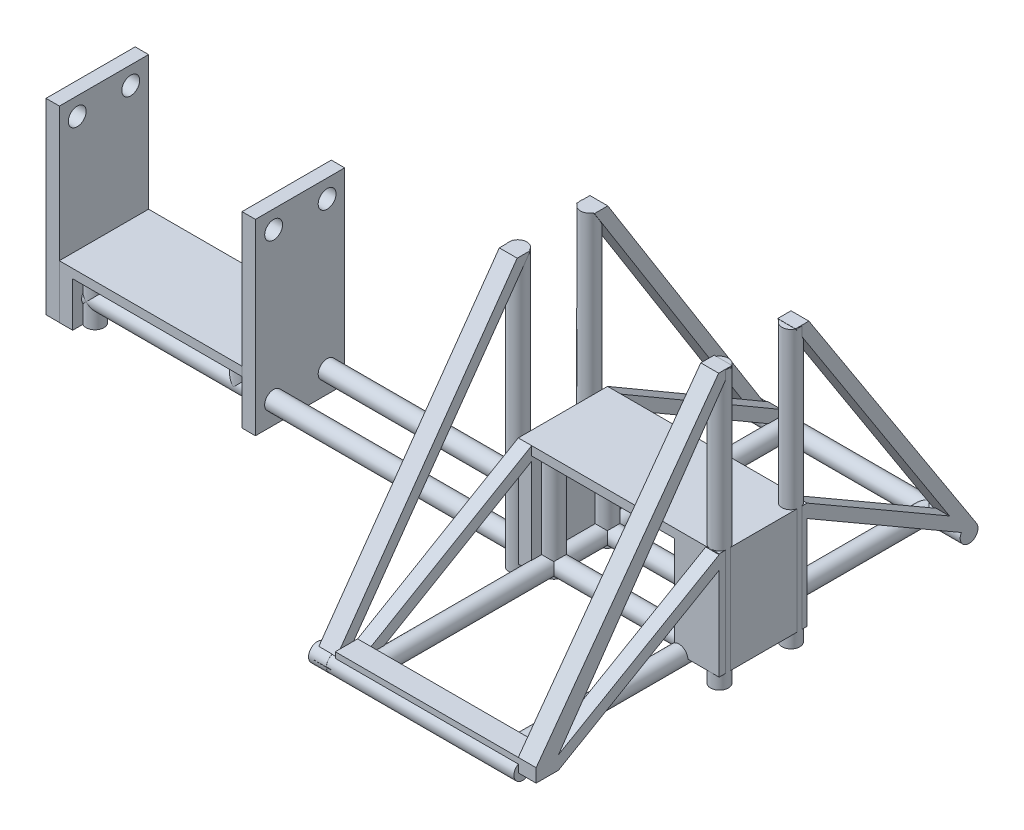
SolidWorks part; units mm, degrees
ref_plane "Front Plane" through (0, 0, 0) normal (0, 0, 1) x (1, 0, 0)
ref_plane "Top Plane" through (0, 0, 0) normal (0, 1, 0) x (1, 0, 0)
ref_plane "Right Plane" through (0, 0, 0) normal (1, 0, 0) x (0, 0, -1)
sketch "Sketch1" plane through (0, 0, 0) normal (0, 1, 0) x (1, 0, 0)
  line L0 (-25.6839, 52.3309) -> (15.3161, 52.3309)
  line L1 (-25.6839, 52.3309) -> (-25.6839, 72.3309)
  line L2 (-25.6839, 72.3309) -> (15.3161, 72.3309)
  line L3 (15.3161, 72.3309) -> (15.3161, 52.3309)
extrude "Boss-Extrude2" add sketch "Sketch1" along normal blind 2
sketch "Sketch2" plane through (0, 0, 0) normal (0, -1, 0) x (-1, 0, 0)
  circle A1 centre (21.6839, 56.3309) radius 2
  circle A4 centre (21.6839, 68.3309) radius 2
  point P2 (21.6839, 56.3309)
  point P3 (0, 0)
  point P14 (0, 0)
extrude "Boss-Extrude5" add sketch "Sketch2" along normal blind 10
sketch "Sketch4" plane through (0, 0, 0) normal (0, -1, 0) x (-1, 0, 0)
  circle A1 centre (-11.3161, 56.3309) radius 2
  circle A2 centre (-11.3161, 68.3309) radius 2
extrude "Boss-Extrude6" add sketch "Sketch4" along normal blind 5
sketch "Sketch5" plane through (15.3161, 0, 0) normal (1, 0, 0) x (0, 0, -1)
  circle A3 centre (56.3309, -4.9901) radius 2
  circle A4 centre (68.3309, -4.9901) radius 2
extrude "Boss-Extrude7" add sketch "Sketch5" against normal blind 38 and the other way blind 100
sketch "Sketch6" plane through (0, 2, 0) normal (0, 1, 0) x (1, 0, 0)
  circle A1 centre (113.1107, 56.3309) radius 2
  circle A2 centre (113.1107, 68.3309) radius 2
  circle A3 centre (81.1107, 68.3309) radius 2
  circle A4 centre (81.1107, 56.3309) radius 2
extrude "Boss-Extrude8" add sketch "Sketch6" along normal blind 15 and the other way blind 9
sketch "Sketch7" plane through (0, 17, 0) normal (0, 1, 0) x (1, 0, 0)
  line L2 (77.1107, 56.3309) -> (77.1107, 52.3666)
  line L4 (77.1107, 52.3666) -> (118.1107, 52.3666)
  line L5 (77.1107, 52.3666) -> (77.1107, 72.3666)
  line L6 (77.1107, 72.3666) -> (118.1107, 72.3666)
  line L7 (118.1107, 52.3666) -> (118.1107, 72.3666)
extrude "Boss-Extrude9" add sketch "Sketch7" along normal blind 2 contours L5 L4 L7 L6
sketch "Sketch8" plane through (0, 0, -52.3666) normal (0, 0, 1) x (1, 0, 0)
  circle A1 centre (81.1107, -4.9901) radius 2
  circle A2 centre (113.1107, -4.9901) radius 2
extrude "Boss-Extrude10" add sketch "Sketch8" along normal blind 40 and the other way blind 56
sketch "Sketch9" plane through (118.1107, 0, 0) normal (1, 0, 0) x (0, 0, -1)
  line L1 (12.3666, -2.9901) -> (12.3666, -6.9901) construction
  line L2 (108.3666, -6.9901) -> (108.3666, -2.9901) construction
  circle A1 centre (12.3666, -4.9901) radius 1.9797
  circle A2 centre (108.3666, -4.9901) radius 2
extrude "Boss-Extrude11" add sketch "Sketch9" against normal blind 42
sketch "Sketch12" plane through (77.1107, 0, 0) normal (-1, 0, 0) x (0, 0, 1)
  line L0 (-52.3666, 19) -> (-52.3666, 17) construction
  line L1 (-52.3666, 19) -> (-72.3666, 19)
  line L2 (-52.3666, 19) -> (-52.3666, -5.472)
  line L3 (-52.3666, -5.472) -> (-72.3666, -5.472)
  line L4 (-72.3666, 19) -> (-72.3666, -5.472)
  point P4 (-72.3666, 19)
  point P6 (-52.3666, 19)
  point P9 (0, 0)
  point P10 (-72.3666, -5.472)
extrude "Boss-Extrude15" add sketch "Sketch12" against normal blind 3
sketch "Sketch14" plane through (0, 19, 0) normal (0, 1, 0) x (1, 0, 0)
  circle A2 centre (75.0364, 70.3666) radius 2
  circle A3 centre (75.0364, 54.3666) radius 2
  circle A4 centre (120.1851, 70.3666) radius 2
  circle A5 centre (120.1851, 54.3666) radius 2
extrude "Boss-Extrude17" add sketch "Sketch14" against normal blind 27 and the other way blind 35
sketch "Sketch15" plane through (118.1107, 0, 0) normal (1, 0, 0) x (0, 0, -1)
  line L1 (52.3666, 19) -> (72.0796, 19)
  line L2 (52.3666, 19) -> (52.3666, -4.9227)
  line L3 (52.3666, -4.9227) -> (72.0796, -4.9227)
  line L4 (72.0796, 19) -> (72.0796, -4.9227)
  point P5 (72.0796, -4.9227)
extrude "Boss-Extrude18" add sketch "Sketch15" along normal blind 4 and the other way blind 6
sketch "Sketch17" plane through (-25.6839, 0, 0) normal (-1, 0, 0) x (0, 0, 1)
  line L1 (-72.3309, 2) -> (-52.3309, 2)
  line L2 (-72.3309, 2) -> (-72.3309, -10)
  line L3 (-72.3309, -10) -> (-52.3309, -10)
  line L4 (-52.3309, 2) -> (-52.3309, -10)
extrude "Boss-Extrude20" add sketch "Sketch17" against normal blind 3
sketch "Sketch19" plane through (15.3161, 0, 0) normal (1, 0, 0) x (0, 0, -1)
  line L7 (52.2692, -9.9436) -> (72.2692, -9.9436)
  line L8 (52.2692, -9.9436) -> (52.2692, 32.0564)
  line L9 (52.2692, 32.0564) -> (72.2692, 32.0564)
  line L10 (72.2692, -9.9436) -> (72.2692, 32.0564)
extrude "Boss-Extrude23" add sketch "Sketch19" along normal blind 3
sketch "Sketch21" plane through (-25.6839, 0, 0) normal (-1, 0, 0) x (0, 0, 1)
  line L1 (-72.3309, -10) -> (-52.349, -10)
  line L2 (-72.3309, -10) -> (-72.3309, 32)
  line L3 (-72.3309, 32) -> (-52.349, 32)
  line L4 (-52.349, -10) -> (-52.349, 32)
extrude "Boss-Extrude24" add sketch "Sketch21" along normal blind 3
sketch "Sketch22" plane through (-28.6839, 0, 0) normal (-1, 0, 0) x (0, 0, 1)
  circle A1 centre (-68.3309, 28) radius 2
  circle A2 centre (-56.349, 28) radius 2
extrude "Cut-Extrude1" cut sketch "Sketch22" against normal blind 52
sketch "Sketch23" plane through (77.1107, 0, 0) normal (-1, 0, 0) x (0, 0, 1)
  line L0 (-72.3666, 19) -> (-72.3666, 16)
  line L2 (-72.3666, 19) -> (-108.3666, -1.9901)
  line L3 (-72.3666, 16) -> (-108.3666, -4.9901)
  line L4 (-108.3666, -1.9901) -> (-108.3666, -4.9901)
  line L5 (-72.3666, 19) -> (-72.3666, -5.472) construction
  line L6 (-62.3666, 19) -> (-62.3666, 7.5165)
  line L7 (-52.3666, 19) -> (-72.3666, 19) construction
  line L8 (-52.3666, 16) -> (-16.3666, -4.9901)
  line L9 (-16.3666, -1.9901) -> (-16.3666, -4.9901)
  line L10 (-52.3666, 19) -> (-16.3666, -1.9901)
  line L11 (-52.3666, 19) -> (-52.3666, 16)
  point P17 (-16.3666, -4.9901)
  point P18 (-16.3666, -4.9901)
  point P19 (0, 0)
  line M10 (-72.3666, 19) -> (-72.3666, -5.472)
  line M16 (-52.3666, -5.472) -> (-52.3666, 19)
extrude "Boss-Extrude25" add sketch "Sketch23" against normal blind 3 contours L2 L4 L3 M10 | L10 L8 L9 M16 region at (77.1107, 7.005, -90.3666) region at (77.1107, 7.005, -34.3666)
sketch "Sketch24" plane through (122.1107, 0, 0) normal (1, 0, 0) x (0, 0, -1)
  line L0 (72.0796, 19) -> (72.0796, 16)
  line L1 (72.0796, 19) -> (108.3666, -1.9901)
  line L2 (72.0796, 16) -> (108.3666, -4.9901)
  line L3 (108.3666, -1.9901) -> (108.3666, -4.9901)
  line L4 (72.0796, -4.9227) -> (72.0796, 19) construction
  line L5 (62.3666, 19) -> (62.3666, 13.064)
  line L6 (69.8263, 19) -> (54.9069, 19) construction
  line L7 (52.6536, 16) -> (16.3666, -4.9901)
  line L8 (16.3666, -1.9901) -> (16.3666, -4.9901)
  line L9 (52.6536, 19) -> (16.3666, -1.9901)
  line L10 (52.6536, 19) -> (52.6536, 16)
extrude "Boss-Extrude26" add sketch "Sketch24" against normal blind 3 contours L10 L9 L8 L7 | L2 L3 L1 L0 region at (122.1107, 7.005, -34.5101)
sketch "Sketch25" plane through (118.1107, 0, 0) normal (1, 0, 0) x (0, 0, -1)
  circle A1 centre (108.3666, -4.9901) radius 2
extrude "Boss-Extrude27" add sketch "Sketch25" along normal blind 4
sketch "Sketch26" plane through (0, 0, -16.3666) normal (0, 0, 1) x (1, 0, 0)
  line L1 (77.1107, -4.9901) -> (122.1107, -4.9901)
  line L2 (77.1107, -4.9901) -> (77.1107, -1.9901)
  line L3 (77.1107, -1.9901) -> (122.1107, -1.9901)
  line L4 (122.1107, -4.9901) -> (122.1107, -1.9901)
  point P4 (0, 0)
  point P5 (76.2247, -2.6666)
  point P6 (77.1107, -1.9901)
  point P8 (77.1107, -4.9901)
  point P10 (104.7634, -1.9901)
  point P11 (122.1107, -1.9901)
extrude "Boss-Extrude28" add sketch "Sketch26" along normal blind 5
sketch "Sketch28" plane through (122.1107, 0, 0) normal (1, 0, 0) x (0, 0, -1)
  line L0 (72.0796, 16) -> (106.6353, -3.9886) construction
  line L1 (11.3666, -1.9901) -> (16.3666, -1.9901)
  line L2 (11.3666, -1.9901) -> (52.2585, 54.1126)
  line L3 (16.3666, -1.9901) -> (55.2585, 54.1126)
  line L4 (52.2585, 54.1126) -> (55.2585, 54.1126)
  line L5 (62.3666, 19) -> (62.3666, 26.0612)
  line L6 (69.8263, 19) -> (54.9069, 19) construction
  line L7 (107.0713, -4.2408) -> (69.4746, 54.1126)
  line L8 (72.4746, 54.1126) -> (69.4746, 54.1126)
  line L9 (110.0536, -3.9158) -> (72.4746, 54.1126)
  line L10 (110.0536, -3.9158) -> (107.0713, -4.2408)
  arc A0 (106.6353, -3.9886) -> (108.3666, -2.9901) centre (108.3666, -4.9901) ccw construction
  point P14 (108.3666, -1.9901)
  point P15 (0, 0)
  point P16 (0, 0)
  point P17 (105.7745, -3.4907)
  point P20 (110.0536, -3.9158)
  point P24 (0, 0)
  point P25 (0, 0)
  point P26 (0, 0)
  point P27 (0, 0)
  line M12 (16.3666, -1.9901) -> (11.3666, -1.9901)
extrude "Boss-Extrude29" add sketch "Sketch28" against normal blind 4 contours L4 L2 L3 M12 | L7 L8 L9 L10 region at (122.1107, 23.7236, -32.1504)
sketch "Sketch30" plane through (77.1107, 0, 0) normal (-1, 0, 0) x (0, 0, 1)
  line L0 (-109.8067, -5.4256) -> (-106.8067, -5.4256)
  line L1 (-109.8067, -5.4256) -> (-72.42, 54)
  line L2 (-106.8067, -5.4256) -> (-69.42, 54)
  line L3 (-72.42, 54) -> (-69.42, 54)
  line L4 (-68.3666, 54) -> (-72.3666, 54) construction
  line L7 (-13.3513, -4.9901) -> (-55.1185, 54)
  line L8 (-52.1185, 54) -> (-55.1185, 54)
  line L9 (-10.3513, -4.9901) -> (-52.1185, 54)
  line L10 (-10.3513, -4.9901) -> (-13.3513, -4.9901)
  point P0 (-13.3513, -4.9901)
extrude "Boss-Extrude30" add sketch "Sketch30" along normal blind 4
sketch "Sketch31" plane through (76.1107, 0, 0) normal (-1, 0, 0) x (0, 0, 1)
  circle A1 centre (-108.3666, -4.9901) radius 2
extrude "Boss-Extrude31" add sketch "Sketch31" along normal blind 4
sketch "Sketch32" plane through (76.1107, 0, 0) normal (-1, 0, 0) x (0, 0, 1)
  circle A1 centre (-12.3666, -4.9901) radius 2
extrude "Boss-Extrude32" add sketch "Sketch32" along normal blind 4
